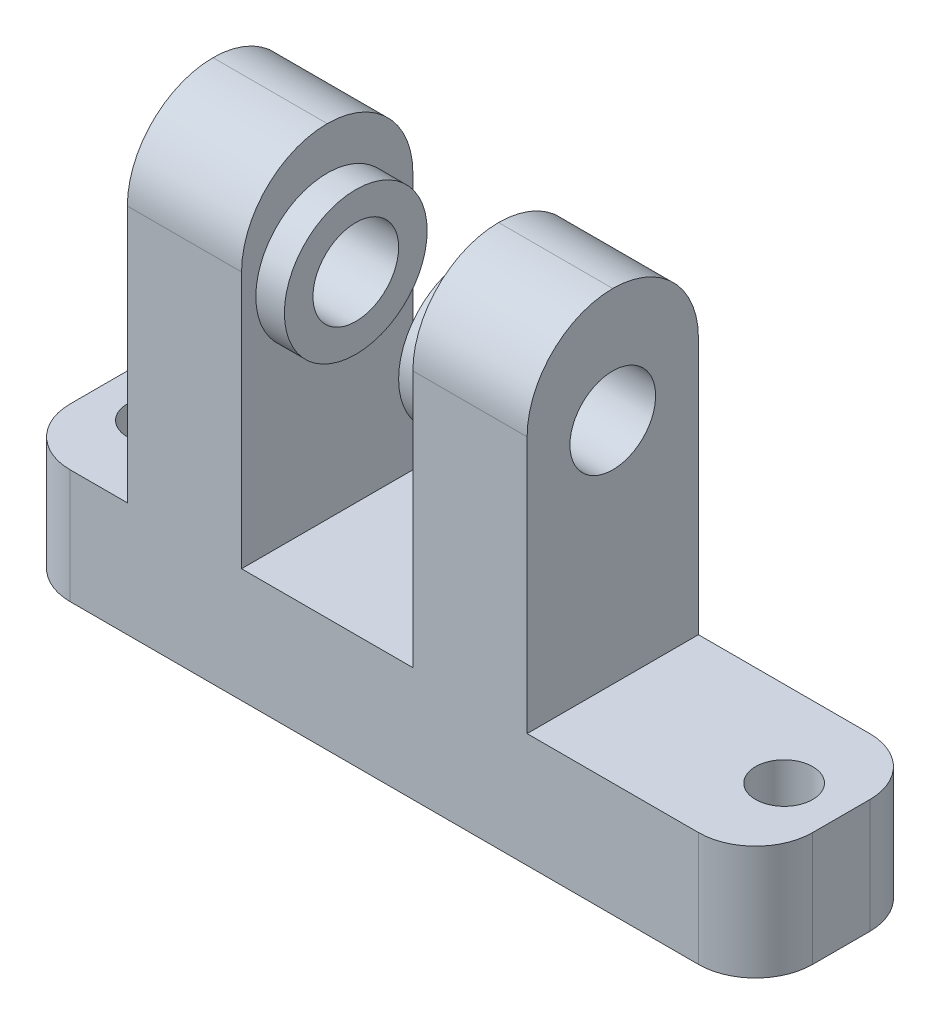
SolidWorks part; units mm, degrees
ref_plane "Front Plane" through (0, 0, 0) normal (0, 0, 1) x (1, 0, 0)
ref_plane "Top Plane" through (0, 0, 0) normal (0, 1, 0) x (1, 0, 0)
ref_plane "Right Plane" through (0, 0, 0) normal (1, 0, 0) x (0, 0, -1)
sketch "Sketch2" plane through (0, 0, 0) normal (0, 1, 0) x (1, 0, 0)
  line L1 (-7, 3) -> (7, 3)
  line L2 (-7, 3) -> (-7, -3)
  line L3 (-7, -3) -> (7, -3)
  line L4 (7, 3) -> (7, -3)
  line L5 (-7, 3) -> (7, -3) construction
  line L6 (-7, -3) -> (7, 3) construction
  point P0 (0, 0)
extrude "Boss-Extrude1" add sketch "Sketch2" along normal blind 4
sketch "Sketch3" plane through (0, 4, 0) normal (0, 1, 0) x (1, 0, 0)
  line L0 (-7, -3) -> (-3, -3)
  line L1 (-7, -3) -> (7, -3) construction
  line L2 (-3, -3) -> (-3, 3)
  line L3 (7, 3) -> (-7, 3) construction
  line L4 (-3, 3) -> (-7, 3)
  line L5 (-7, 3) -> (-7, -3)
  line L6 (7, -3) -> (3, -3)
  line L7 (3, -3) -> (3, 3)
  line L8 (3, 3) -> (7, 3)
  line L9 (7, 3) -> (7, -3)
extrude "Boss-Extrude2" add sketch "Sketch3" along normal blind 12
sketch "Sketch4" plane through (7, 0, 0) normal (1, 0, 0) x (0, 0, -1)
  circle A0 centre (0, 12) radius 1.5
extrude "Cut-Extrude1" cut sketch "Sketch4" against normal through all both and the other way through all
sketch "Sketch5" plane through (-3, 0, 0) normal (1, 0, 0) x (0, 0, -1)
  circle A0 centre (0, 12) radius 1.5
  circle A1 centre (0, 12) radius 2.5
extrude "Boss-Extrude3" add sketch "Sketch5" along normal blind 1
sketch "Sketch6" plane through (3, 0, 0) normal (-1, 0, 0) x (0, 0, 1)
  circle A0 centre (0, 12) radius 1.5
  circle A1 centre (0, 12) radius 2.5
extrude "Boss-Extrude4" add sketch "Sketch6" along normal blind 1
sketch "Sketch7" plane through (0, 4, 0) normal (0, 1, 0) x (1, 0, 0)
  line L2 (15, 3) -> (15, -3)
  line L3 (15, -3) -> (7, -3)
  line L4 (-7, -3) -> (-7, 3)
  line L5 (-7, 3) -> (-7, -3) construction
  line L6 (-7, 3) -> (-11, 3)
  line L7 (-11, 3) -> (-11, -3)
  line L8 (-11, -3) -> (-7, -3)
  line L9 (15, 3) -> (7, 3)
  line L10 (7, 3) -> (7, -3)
  circle A0 centre (13, 0) radius 1
  circle A1 centre (-9, 0) radius 1
extrude "Boss-Extrude5" add sketch "Sketch7" against normal blind 4
fillet "Fillet1" radius 2 4 edges at (-11, 2, -3) (-11, 2, 3) (15, 2, 3) (15, 2, -3)
fillet "Fillet2" radius 3 4 edges at (-5, 16, -3) (5, 16, -3) (5, 16, 3) (-5, 16, 3)
